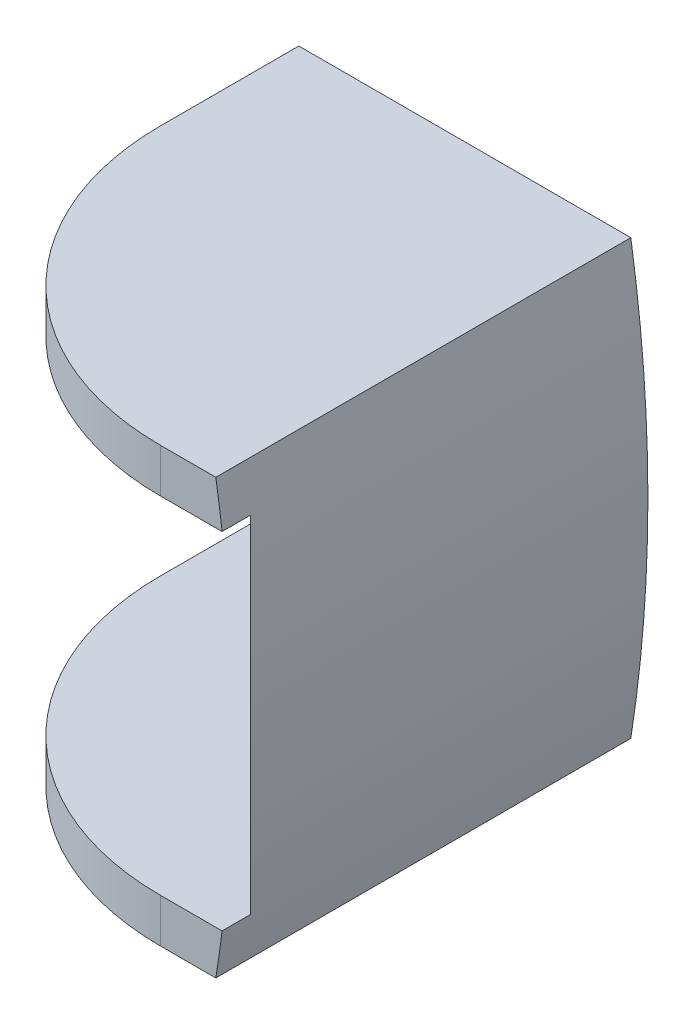
SolidWorks part; units mm, degrees
ref_plane "Front Plane" through (0, 0, 0) normal (0, 0, 1) x (1, 0, 0)
ref_plane "Top Plane" through (0, 0, 0) normal (0, 1, 0) x (1, 0, 0)
ref_plane "Right Plane" through (0, 0, 0) normal (1, 0, 0) x (0, 0, -1)
sketch "Sketch6" plane through (0, 0, 0) normal (0, 1, 0) x (1, 0, 0)
  line L1 (-12, 15) -> (12, 15)
  line L2 (-12, 15) -> (-12, -15)
  line L3 (-12, -15) -> (12, -15)
  line L4 (12, 15) -> (12, -15)
  line L5 (-12, 15) -> (12, -15) construction
  line L6 (-12, -15) -> (12, 15) construction
  point P0 (0, 0)
  dimension "D1" = 24
  dimension "D2" = 30
extrude "Boss-Extrude5" add sketch "Sketch6" along normal blind 31.35
sketch "Sketch10" plane through (0, 0, -15) normal (0, 0, -1) x (-1, 0, 0)
  line L0 (-12, 0) -> (-12, 31.35)
  arc A1 (-12, 0) -> (-12, 31.35) centre (86.7638, 15.675) cw
  dimension "D1" = 100
extrude "Boss-Extrude6" add sketch "Sketch10" against normal up to surface (30 mm away) up to face at (0, 15.675, 15)
ref_plane "Plane1" through (0, 15.675, 0) normal (0, 1, 0) x (1, 0, 0)
sketch "Sketch8" plane through (0, 15.675, 0) normal (0, 1, 0) x (1, 0, 0)
  line L0 (-12, 11.5) -> (-12, -15)
  line L1 (-12, 15) -> (-12, -15) construction
  line L4 (14.5, -15) -> (-12, 11.5)
  line L5 (12, 15) -> (-12, 15) construction
  line L6 (-12, -15) -> (14.5, -15)
  line L7 (-12, -15) -> (12, -15) construction
  dimension "D1" = 3.5
  dimension "D2" = 45
extrude "Cut-Extrude1" cut sketch "Sketch8" against normal offset from surface (12.5 mm away) 3.175 up to face at (0, 0, 0)
mirror "Mirror2" about plane through (0, 15.675, 0) normal (0, 1, 0) of "Cut-Extrude1"
fillet "Fillet1" radius 20 2 edges at (-12, 1.5875, 15) (-12, 29.7625, 15)
sketch "Sketch9" plane through (0, 0, -15) normal (0, 0, -1) x (-1, 0, 0)
  line L0 (12, 15.675) -> (-13.2362, 15.675) construction
  line L3 (12, 31.35) -> (12, 0) construction
  circle A0 centre (2.7638, 15.675) radius 2.15
  circle A1 centre (-7.2362, 15.675) radius 2.15
  arc A3 (-12, 31.35) -> (-12, 0) centre (86.7638, 15.675) ccw construction
  point P11 (0, 0)
  point P12 (0, 0)
  dimension "D1" = 4.3
  dimension "D2" = 10
  dimension "D3" = 6
extrude "Cut-Extrude2" cut sketch "Sketch9" against normal blind 8
